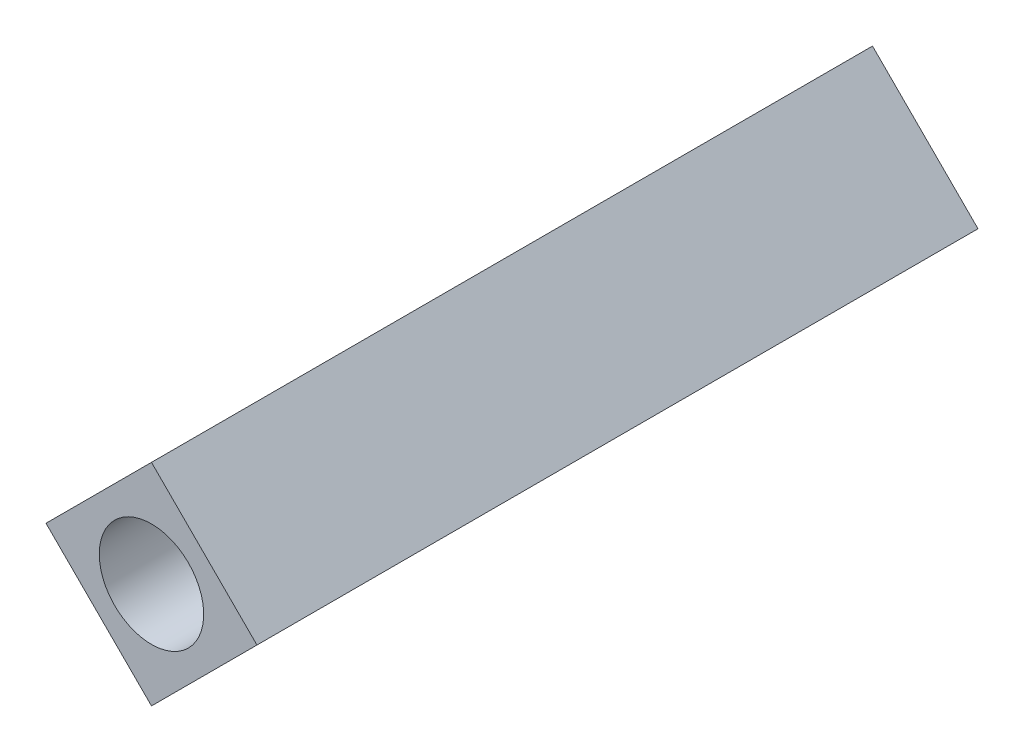
SolidWorks part; units mm, degrees
ref_plane "正面" through (0, 0, 0) normal (0, 0, 1) x (1, 0, 0)
ref_plane "平面" through (0, 0, 0) normal (0, 1, 0) x (1, 0, 0)
ref_plane "右側面" through (0, 0, 0) normal (1, 0, 0) x (0, 0, -1)
sketch "ｽｹｯﾁ1" plane through (0, 0, 0) normal (0, 0, 1) x (1, 0, 0)
  line L1 (4.2426, 0) -> (0, 4.2426)
  line L2 (0, 4.2426) -> (-4.2426, 0)
  line L3 (-4.2426, 0) -> (0, -4.2426)
  line L4 (0, -4.2426) -> (4.2426, 0)
  circle A0 centre (0, 0) radius 2.1
  circle A1 centre (0, 0) radius 3 construction
  dimension "D1" = 4.2
  dimension "D2" = 6
extrude "ﾎﾞｽ - 押し出し1" add sketch "ｽｹｯﾁ1" along normal blind 29
